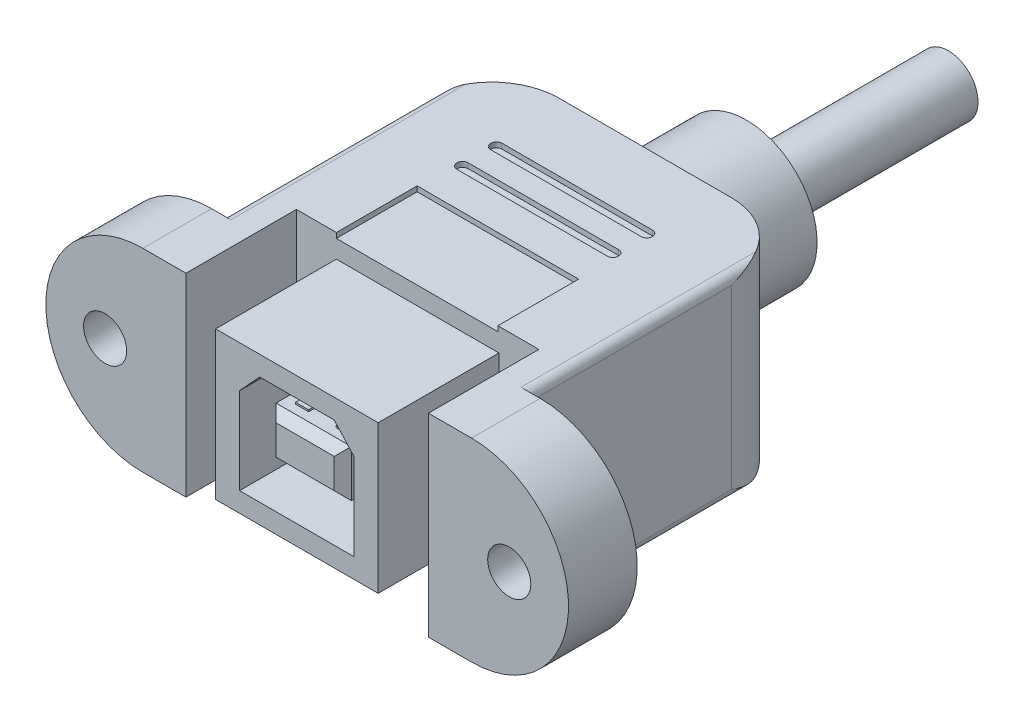
SolidWorks part; units mm, degrees
ref_plane "Front Plane" through (0, 0, 0) normal (0, 0, 1) x (1, 0, 0)
ref_plane "Top Plane" through (0, 0, 0) normal (0, 1, 0) x (1, 0, 0)
ref_plane "Right Plane" through (0, 0, 0) normal (1, 0, 0) x (0, 0, -1)
sketch "Sketch1" plane through (0, 0, 0) normal (0, 0, 1) x (1, 0, 0)
  line L0 (-19.4, 0) -> (-15, 0) construction
  line L1 (-12.2, -7.2) -> (12.2, -7.2)
  line L2 (-15, 0) -> (0, 0) construction
  line L3 (-12.2, 7.2) -> (12.2, 7.2)
  line L4 (0, 0) -> (15, 0) construction
  line L5 (0, 7.2) -> (0, 0) construction
  line L6 (15, 0) -> (19.4, 0) construction
  line L7 (0, 0) -> (0, -7.2) construction
  arc A0 (-12.2, -7.2) -> (-12.2, 7.2) centre (-12.2, 0) cw
  arc A1 (12.2, 7.2) -> (12.2, -7.2) centre (12.2, 0) cw
  circle A6 centre (-15, 0) radius 1.6
  circle A7 centre (15, 0) radius 1.6
  point P1 (20.1168, 14.45)
  point P3 (20.1168, 0)
  point P28 (0, 14.45)
  dimension "D3" = 3.2
  dimension "D7" = 30
  dimension "D1" = 14.4
  dimension "D2" = 38.8
extrude "Boss-Extrude1" add sketch "Sketch1" along normal blind 5.1
sketch "Sketch2" plane through (0, 0, 0) normal (0, 0, -1) x (-1, 0, 0)
  line L0 (12.2, -7.2) -> (-12.2, -7.2) construction
  line L1 (-10.765, 7.2) -> (10.765, 7.2)
  line L2 (-11.4, 6.565) -> (-11.4, -6.565)
  line L3 (-10.765, -7.2) -> (10.765, -7.2)
  line L4 (11.4, 6.565) -> (11.4, -6.565)
  line L5 (-12.2, 7.2) -> (12.2, 7.2) construction
  line L6 (-11.4, 0) -> (0, 0) construction
  line L7 (0, 0) -> (11.4, 0) construction
  arc A0 (-11.4, -6.565) -> (-10.765, -7.2) centre (-10.765, -6.565) ccw
  arc A1 (10.765, -7.2) -> (11.4, -6.565) centre (10.765, -6.565) ccw
  arc A2 (10.765, 7.2) -> (11.4, 6.565) centre (10.765, 6.565) cw
  arc A3 (-10.765, 7.2) -> (-11.4, 6.565) centre (-10.765, 6.565) ccw
  point P9 (0, 0)
  dimension "D1" = 0.635
  dimension "D2" = 22.8
extrude "Boss-Extrude2" add sketch "Sketch2" along normal blind 20
sketch "Sketch3" plane through (0, 0, -20) normal (0, 0, -1) x (-1, 0, 0)
  circle A0 centre (0, 0) radius 5.25
  dimension "D1" = 10.5
extrude "Boss-Extrude3" add sketch "Sketch3" along normal blind 7.5
sketch "Sketch4" plane through (0, 0, -27.5) normal (0, 0, -1) x (-1, 0, 0)
  circle A0 centre (0, 0) radius 2.2
  dimension "D1" = 4.4
extrude "Boss-Extrude4" add sketch "Sketch4" along normal blind 15
sketch "Sketch11" plane through (0, 7.2, 0) normal (0, 1, 0) x (1, 0, 0)
  line L0 (12.2, -5.1) -> (-12.2, -5.1) construction
  line L1 (-9, -5.1) -> (9, -5.1)
  line L2 (-9, -5.1) -> (-9, 3.1)
  line L3 (-9, 3.1) -> (9, 3.1)
  line L4 (9, -5.1) -> (9, 3.1)
  line L5 (0, 3.1) -> (0, 0) construction
  dimension "D1" = 18
  dimension "D2" = 8.2
extrude "Cut-Extrude3" cut sketch "Sketch11" against normal through all
sketch "Sketch5" plane through (0, 0, 5.1) normal (0, 0, 1) x (1, 0, 0)
  line L0 (0, 0) -> (0, 5.4864) construction
  line L1 (-6.0325, 5.4864) -> (6.0325, 5.4864)
  line L2 (-6.0325, 5.4864) -> (-6.0325, -5.4864)
  line L3 (-6.0325, -5.4864) -> (6.0325, -5.4864)
  line L4 (6.0325, 5.4864) -> (6.0325, -5.4864)
  circle A0 centre (15, 0) radius 1.6 construction
  dimension "D2" = 5.4864
  dimension "D3" = 10.9728
  dimension "D4" = 12.065
extrude "Boss-Extrude5" add sketch "Sketch5" along normal blind 0.762
sketch "Sketch12" plane through (0, 0, -3.1) normal (0, 0, 1) x (1, 0, 0)
  line L1 (-6.0325, 5.4864) -> (6.0325, 5.4864)
  line L2 (-6.0325, 5.4864) -> (-6.0325, -5.4864)
  line L3 (-6.0325, -5.4864) -> (6.0325, -5.4864)
  line L4 (6.0325, 5.4864) -> (6.0325, -5.4864)
extrude "Boss-Extrude9" add sketch "Sketch12" along normal up to surface (8.2 mm away) up to face at (0, 0, 5.1)
sketch "Sketch6" plane through (0, 0, 5.862) normal (0, 0, 1) x (1, 0, 0)
  line L0 (-4.2545, 2.4003) -> (-4.2545, -4.0259)
  line L5 (-4.2545, -4.0259) -> (4.2545, -4.0259)
  line L6 (4.2545, 2.4003) -> (4.2545, -4.0259)
  line L8 (-2.7686, 4.0259) -> (2.7686, 4.0259)
  line L9 (0, 4.0259) -> (0, -4.0259) construction
  line L13 (-2.7686, 4.0259) -> (-4.2545, 2.4003)
  line L18 (2.7686, 4.0259) -> (4.2545, 2.4003)
  point P6 (5.8039, 10.5664)
  point P9 (14.3129, 10.5664)
  point P10 (4.0259, 11.2014)
  point P11 (16.0909, 11.2014)
  point P14 (7.2898, 12.3444)
  point P15 (7.2898, 1.3716)
  point P16 (12.827, 12.3444)
  point P17 (12.827, 1.3716)
  point P18 (4.0259, 9.5758)
  point P19 (16.0909, 9.5758)
  dimension "D1" = 8.0518
  dimension "D2" = 8.509
  dimension "D3" = 5.5372
  dimension "D4" = 8.509
  dimension "D5" = 1.4859
  dimension "D6" = 1.6256
extrude "Cut-Extrude1" cut sketch "Sketch6" against normal blind 8.89
sketch "Sketch7" plane through (0, 0, -3.028) normal (0, 0, 1) x (1, 0, 0)
  line L0 (0, 4.0259) -> (0, -4.0259) construction
  line L1 (2.7686, 4.0259) -> (-2.7686, 4.0259) construction
  line L2 (-4.2545, -4.0259) -> (4.2545, -4.0259) construction
  line L3 (4.2545, -0.8128) -> (-4.2545, -0.8128) construction
  line L4 (4.2545, -4.0259) -> (4.2545, 2.4003) construction
  line L5 (-4.2545, 2.4003) -> (-4.2545, -4.0259) construction
  line L6 (-2.7686, 1.7399) -> (-2.7686, -1.7399)
  line L7 (2.8194, 1.7399) -> (2.8194, -1.7399)
  line L8 (-4.2545, -4.0259) -> (4.2545, -4.0259) construction
  line L9 (-2.7686, 4.0259) -> (2.8194, 4.0259) construction
  line L10 (-2.7686, -1.7399) -> (2.8194, -1.7399)
  line L11 (-2.7686, 1.7399) -> (2.8194, 1.7399)
  line L12 (-2.7686, 0) -> (0, 0) construction
  line L13 (-2.7686, 4.0259) -> (-2.7686, -4.0259) construction
  line L14 (2.8194, 4.0259) -> (2.8194, -4.0259) construction
  line L15 (-4.2545, -1.7399) -> (4.2545, -1.7399) construction
  dimension "D1" = 3.4798
  dimension "D2" = 5.588
extrude "Boss-Extrude6" add sketch "Sketch7" along normal blind 8.3058
chamfer "Chamfer1" distance 0.635 angle 45 4 edges at (-2.7686, 0, 5.2778) (0.0254, -1.7399, 5.2778) (2.8194, 0, 5.2778) (0.0254, 1.7399, 5.2778)
sketch "Sketch8" plane through (0, 1.7399, 0) normal (0, 1, 0) x (1, 0, 0)
  line L0 (2.8194, 3.028) -> (-2.7686, 3.028) construction
  line L1 (-1.9633, 3.028) -> (-0.9959, 3.028)
  line L2 (-1.9633, 3.028) -> (-1.9633, -3.9955)
  line L3 (-1.9633, -3.9955) -> (-0.9959, -3.9955)
  line L4 (-0.9959, 3.028) -> (-0.9959, -3.9955)
  line L5 (0.0254, -5.2778) -> (0.0254, -3.2159) construction
  line L6 (1.0467, 3.028) -> (1.0467, -3.9955)
  line L7 (2.0141, -3.9955) -> (1.0467, -3.9955)
  line L8 (2.0141, 3.028) -> (2.0141, -3.9955)
  line L9 (2.0141, 3.028) -> (1.0467, 3.028)
  line L10 (2.1844, -5.2778) -> (-2.1336, -5.2778) construction
  dimension "D1" = 0.9674
  dimension "D2" = 2.0425
  dimension "D3" = 7.0235
extrude "Boss-Extrude7" add sketch "Sketch8" along normal blind 0.127
ref_plane "Plane1" through (0, 0, 0) normal (0, -1, 0) x (1, 0, 0)
mirror "Mirror1" about plane through (0, 0, 0) normal (0, -1, 0) of "Boss-Extrude7"
sketch "Sketch9" plane through (0, 7.2, 0) normal (0, 1, 0) x (1, 0, 0)
  line L0 (-0.0381, 14.149) -> (-0.0381, 11.6344) construction
  line L1 (-6.0325, 9.0944) -> (5.9563, 9.0944)
  line L2 (-6.0325, 9.0944) -> (-6.0325, 3.1)
  line L3 (-6.0325, 3.1) -> (5.9563, 3.1)
  line L4 (5.9563, 9.0944) -> (5.9563, 3.1)
  line L5 (-5.6261, 12.4726) -> (5.5499, 12.4726)
  line L6 (-6.0325, 12.0662) -> (-6.0325, 12.0408)
  line L7 (-5.6261, 11.6344) -> (5.5499, 11.6344)
  line L8 (5.9563, 12.0662) -> (5.9563, 12.0408)
  line L9 (-5.6261, 14.9872) -> (5.5499, 14.9872)
  line L10 (-6.0325, 14.5808) -> (-6.0325, 14.5554)
  line L11 (-5.6261, 14.149) -> (5.5499, 14.149)
  line L12 (5.9563, 14.5808) -> (5.9563, 14.5554)
  line L13 (-0.0381, 11.6344) -> (-0.0381, 9.0944) construction
  line L14 (9, 3.1) -> (-9, 3.1) construction
  line L15 (6.0325, 3.1) -> (-6.0325, 3.1) construction
  arc A0 (5.5499, 14.9872) -> (5.9563, 14.5808) centre (5.5499, 14.5808) cw
  arc A1 (5.5499, 14.149) -> (5.9563, 14.5554) centre (5.5499, 14.5554) ccw
  arc A2 (5.5499, 12.4726) -> (5.9563, 12.0662) centre (5.5499, 12.0662) cw
  arc A3 (5.5499, 11.6344) -> (5.9563, 12.0408) centre (5.5499, 12.0408) ccw
  arc A4 (-6.0325, 12.0408) -> (-5.6261, 11.6344) centre (-5.6261, 12.0408) ccw
  arc A5 (-5.6261, 12.4726) -> (-6.0325, 12.0662) centre (-5.6261, 12.0662) ccw
  arc A6 (-6.0325, 14.5554) -> (-5.6261, 14.149) centre (-5.6261, 14.5554) ccw
  arc A7 (-5.6261, 14.9872) -> (-6.0325, 14.5808) centre (-5.6261, 14.5808) ccw
  point P20 (5.9563, 14.149)
  point P25 (5.9563, 11.6344)
  point P28 (-6.0325, 11.6344)
  point P33 (-6.0325, 14.149)
  point P36 (-6.0325, 14.9872)
  dimension "D11" = 0.4064
  dimension "D2" = 5.9944
  dimension "D3" = 2.54
  dimension "D4" = 0.8382
  dimension "D5" = 0.8382
  dimension "D6" = 1.6764
  dimension "D8" = 11.9888
  dimension "D9" = 11.9888
  dimension "D10" = 11.9888
extrude "Cut-Extrude2" cut sketch "Sketch9" against normal blind 0.381
ref_plane "Plane2" through (0, 0, 0) normal (0, 1, 0) x (-1, 0, 0)
mirror "Mirror3" about plane through (0, 0, 0) normal (0, 1, 0) of "Cut-Extrude2"
sketch "Sketch10" plane through (0, 6.819, 0) normal (0, 1, 0) x (1, 0, 0)
  line L0 (4.3979, 2.5403) -> (5.4832, 1.9137)
  line L1 (6.4231, 3.7935) -> (6.4231, 5.0467)
  line L2 (6.4231, 3.7935) -> (7.6763, 3.7935)
  line L3 (7.6763, 3.7935) -> (7.6763, 4.2133)
  line L4 (6.4231, 5.0467) -> (7.6763, 5.0467)
  line L5 (5.4832, 1.9137) -> (5.4832, 2.3335)
  line L6 (5.4832, 2.3335) -> (12.1084, 2.3335)
  line L7 (12.1084, 2.3335) -> (11.0911, 1.2589)
  line L8 (4.3979, 2.5403) -> (5.4832, 3.1669)
  line L9 (5.4832, 3.1669) -> (5.4832, 2.7471)
  line L10 (5.4832, 2.7471) -> (10.3289, 2.7471)
  line L11 (10.3289, 2.7471) -> (9.3116, 3.8217)
  line L12 (7.6763, 4.2133) -> (8.4015, 4.2133)
  line L13 (7.6763, 4.6269) -> (8.4015, 4.6269)
  line L14 (7.6763, 4.6269) -> (7.6763, 5.0467)
  line L15 (9.2078, 0.8673) -> (10.1811, 0.8673)
  line L16 (9.2078, 0.4537) -> (10.1811, 0.4537)
  line L17 (12.6779, 2.3335) -> (13.4367, 2.3335)
  line L18 (10.8983, 2.7471) -> (13.4367, 2.7471)
  line L19 (12.6779, 2.3335) -> (11.3915, 0.9746)
  line L20 (10.8983, 2.7471) -> (9.6119, 4.106)
  arc A0 (13.4367, 2.3335) -> (13.4367, 2.7471) centre (14.4625, 2.5403) ccw
  arc A1 (9.2078, 0.8673) -> (9.2078, 0.4537) centre (8.6162, 0.6605) ccw
  arc A2 (11.0911, 1.2589) -> (10.1811, 0.8673) centre (10.1811, 2.1205) cw
  arc A3 (11.3915, 0.9746) -> (10.1811, 0.4537) centre (10.1811, 2.1205) cw
  arc A4 (9.3116, 3.8217) -> (8.4015, 4.2133) centre (8.4015, 2.9601) ccw
  arc A5 (9.6119, 4.106) -> (8.4015, 4.6269) centre (8.4015, 2.9601) ccw
extrude "Boss-Extrude8" [suppressed] add sketch "Sketch10" along normal blind 0.381
fillet "Fillet1" radius 5 2 edges at (11.4, 0, -20) (-11.4, 0, -20)
